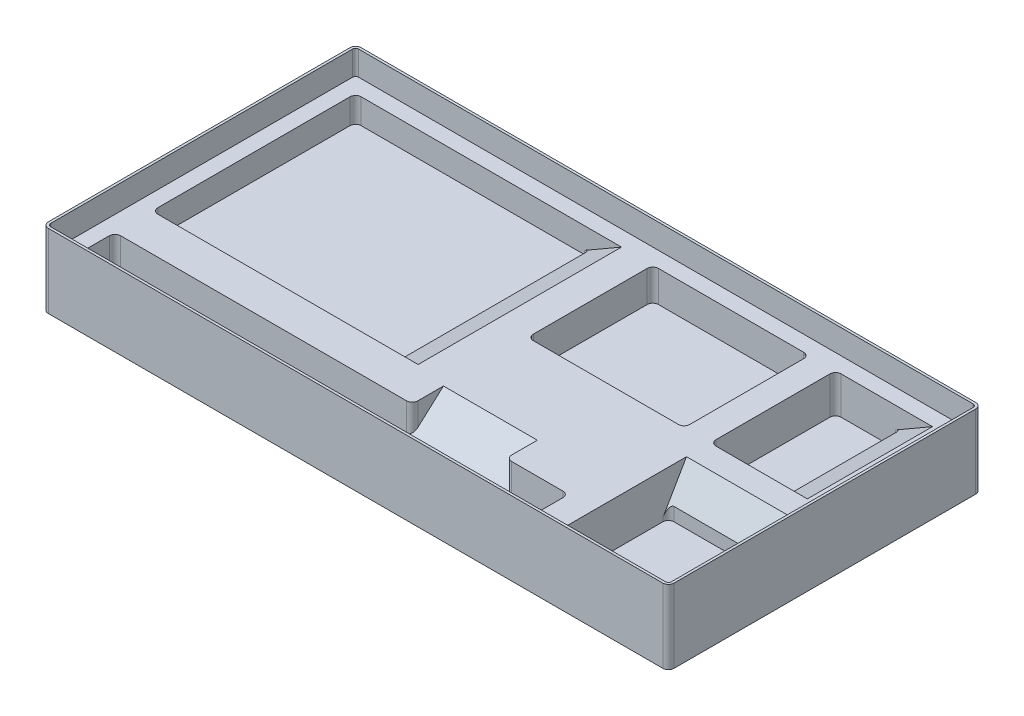
SolidWorks part; units mm, degrees
note: The reader was unsure of these and kept them because the rebuilt part matched: shared geometry of "Sketch3<3>", "Sketch3<4>", "Sketch3<5>", "Sketch3<6>", "Sketch3<7>".
other "Camera1"
ref_plane "Front Plane" through (0, 0, 0) normal (0, 0, 1) x (1, 0, 0)
ref_plane "Top Plane" through (0, 0, 0) normal (0, 1, 0) x (1, 0, 0)
ref_plane "Right Plane" through (0, 0, 0) normal (1, 0, 0) x (0, 0, -1)
sketch "Sketch1" plane through (0, 0, 0) normal (0, 1, 0) x (1, 0, 0)
  line L1 (100, -50) -> (-100, -50)
  line L2 (100, -50) -> (100, 50)
  line L3 (100, 50) -> (-100, 50)
  line L4 (-100, -50) -> (-100, 50)
  line L5 (0, 50) -> (0, -50) construction
  line L6 (100, 0) -> (-100, 0) construction
  point P0 (0, 0)
  dimension "D1" = 200
  dimension "D2" = 100
extrude "Boss-Extrude1" add sketch "Sketch1" against normal blind 0.8
sketch "Sketch2" plane through (0, 0, 0) normal (0, 1, 0) x (1, 0, 0)
  line L0 (-99.2, 49.2) -> (-99.2, -49.2)
  line L1 (-99.2, -49.2) -> (99.2, -49.2)
  line L2 (99.2, -49.2) -> (99.2, 49.2)
  line L3 (99.2, 49.2) -> (-99.2, 49.2)
  line L4 (-100, 50) -> (-100, -50)
  line L5 (-100, -50) -> (100, -50)
  line L6 (100, -50) -> (100, 50)
  line L7 (100, 50) -> (-100, 50)
  line L8 (-100, 50) -> (-100, -50)
  line L9 (-100, -50) -> (100, -50)
  line L10 (100, -50) -> (100, 50)
  line L11 (100, 50) -> (-100, 50)
  dimension "D1" = 0
  dimension "D2" = 0.8
extrude "Boss-Extrude2" add sketch "Sketch2" along normal blind 15 contours L2 L3 L0 L1 | L10 L11 L8 L9 L3 L2 L1 L0
sketch "Sketch3" plane through (0, 15, 0) normal (0, 1, 0) x (1, 0, 0)
  line L0 (0, 44.2) -> (0, 49.2) construction
  line L1 (59.2, 4.2) -> (80.2, 4.2)
  line L2 (59.2, 4.2) -> (59.2, 44.2)
  line L3 (59.2, 44.2) -> (80.2, 44.2)
  line L4 (-100, 50) -> (-100, -50)
  line L5 (-100, -50) -> (100, -50)
  line L6 (100, -50) -> (100, 50)
  line L7 (100, 50) -> (-100, 50)
  line L8 (-100, 50) -> (-100, -50) construction
  line L9 (-100, -50) -> (100, -50) construction
  line L10 (100, -50) -> (100, 50) construction
  line L11 (100, 50) -> (-100, 50) construction
  line L12 (-99.2, 49.2) -> (-99.2, -49.2)
  line L13 (-99.2, -49.2) -> (99.2, -49.2)
  line L14 (99.2, -49.2) -> (99.2, 49.2)
  line L15 (99.2, 49.2) -> (-99.2, 49.2)
  line L16 (-99.2, 49.2) -> (-99.2, -49.2) construction
  line L17 (-99.2, -49.2) -> (99.2, -49.2) construction
  line L18 (99.2, -49.2) -> (99.2, 49.2) construction
  line L19 (99.2, 49.2) -> (-99.2, 49.2) construction
  line L20 (80.2, 4.2) -> (80.2, 44.2)
  line L21 (69.7, 44.2) -> (69.7, 4.2) construction
  line L22 (59.2, 24.2) -> (80.2, 24.2) construction
  line L23 (59.2, -9.2) -> (94.2, -9.2)
  line L24 (59.2, -9.2) -> (59.2, -44.2)
  line L25 (59.2, -44.2) -> (94.2, -44.2)
  line L26 (94.2, -9.2) -> (94.2, -44.2)
  line L27 (76.7, -44.2) -> (76.7, -9.2) construction
  line L28 (59.2, -26.7) -> (94.2, -26.7) construction
  line L29 (0.8, 4.2) -> (50.8, 4.2)
  line L30 (0.8, 4.2) -> (0.8, 44.2)
  line L31 (0.8, 44.2) -> (50.8, 44.2)
  line L32 (50.8, 4.2) -> (50.8, 44.2)
  line L33 (25.8, 44.2) -> (25.8, 4.2) construction
  line L34 (0.8, 24.2) -> (50.8, 24.2) construction
  line L35 (-94.2, -20.8) -> (-19.2, -20.8)
  line L36 (-94.2, -20.8) -> (-94.2, 44.2)
  line L37 (-94.2, 44.2) -> (-19.2, 44.2)
  line L38 (-19.2, -20.8) -> (-19.2, 44.2)
  line L39 (-56.7, 44.2) -> (-56.7, -20.8) construction
  line L40 (-94.2, 11.7) -> (-19.2, 11.7) construction
  line L41 (-94.2, -44.2) -> (50.8, -44.2)
  line L42 (-94.2, -44.2) -> (-94.2, -32.7)
  line L43 (-94.2, -32.7) -> (50.8, -32.7)
  line L44 (50.8, -44.2) -> (50.8, -32.7)
  line L45 (-21.7, -32.7) -> (-21.7, -44.2) construction
  line L46 (-94.2, -38.45) -> (50.8, -38.45) construction
  line L47 (-94.2, -44.2) -> (94.2, -44.2) construction
  line L48 (-94.2, -44.2) -> (-94.2, 44.2) construction
  line L49 (-94.2, 44.2) -> (94.2, 44.2) construction
  line L50 (94.2, -44.2) -> (94.2, 44.2) construction
  line L51 (0, -49.2) -> (0, -44.2) construction
  line L52 (94.2, 0) -> (99.2, 0) construction
  line L53 (-99.2, 0) -> (-94.2, 0) construction
  line L55 (30.8, -32.7) -> (0.8, -32.7)
  line L56 (30.8, -32.7) -> (30.8, -22.7)
  line L57 (30.8, -22.7) -> (0.8, -22.7)
  line L58 (0.8, -32.7) -> (0.8, -22.7)
  line L59 (-9.2, -0.8) -> (-19.2, -0.8)
  line L60 (-9.2, -0.8) -> (-9.2, 24.2)
  line L61 (-9.2, 24.2) -> (-19.2, 24.2)
  line L62 (-19.2, -0.8) -> (-19.2, 24.2)
  line L63 (-14.2, 24.2) -> (-14.2, -0.8) construction
  line L64 (-9.2, 11.7) -> (-19.2, 11.7) construction
  line L65 (64.2, 0.8) -> (89.2, 0.8)
  line L66 (64.2, 0.8) -> (64.2, -9.2)
  line L67 (64.2, -9.2) -> (89.2, -9.2)
  line L68 (89.2, 0.8) -> (89.2, -9.2)
  line L69 (76.7, -9.2) -> (76.7, 0.8) construction
  line L70 (64.2, -4.2) -> (89.2, -4.2) construction
  point P6 (69.7, 24.2)
  point P12 (76.7, -26.7)
  point P19 (25.8, 24.2)
  point P26 (-56.7, 11.7)
  point P33 (-21.7, -38.45)
  point P53 (-14.2, 11.7)
  point P66 (76.7, -4.2)
  dimension "D3" = 75
  dimension "D4" = 65
  dimension "D5" = 145
  dimension "D6" = 11.5
  dimension "D7" = 35
  dimension "D8" = 35
  dimension "D9" = 40
  dimension "D10" = 50
  dimension "D11" = 21
  dimension "D12" = 40
  dimension "D13" = 5
  dimension "D14" = 5
  dimension "D15" = 10
  dimension "D16" = 30
  dimension "D17" = 20
  dimension "D18" = 25
  dimension "D19" = 10
  dimension "D20" = 10
  dimension "D21" = 25
  dimension "D1" = 0
  dimension "D2" = 0
extrude "Blender" cut sketch "Sketch3" against normal blind 12 contours L41 L44 L43 L42
extrude "Charcoals" cut sketch "Sketch3<3>" against normal blind 8 contours L35 L38 L37 L36
sketch "Sketch3<3>" plane through (0, 15, 0) normal (0, 1, 0) x (1, 0, 0) same geometry as "Sketch3"
extrude "Rubber" cut sketch "Sketch3<4>" against normal blind 10 contours L29 L32 L31 L30
sketch "Sketch3<4>" plane through (0, 15, 0) normal (0, 1, 0) x (1, 0, 0) same geometry as "Sketch3"
extrude "Eraser" cut sketch "Sketch3<5>" against normal blind 12 contours L1 L20 L3 L2
sketch "Sketch3<5>" plane through (0, 15, 0) normal (0, 1, 0) x (1, 0, 0) same geometry as "Sketch3"
extrude "Sharpener" cut sketch "Sketch3<6>" against normal blind 14.25 contours L26 L23 L24 L25
sketch "Sketch3<6>" plane through (0, 15, 0) normal (0, 1, 0) x (1, 0, 0) same geometry as "Sketch3"
chamfer "Chamfer1" distance 10 angle 30 3 edges at (76.7, 15, 9.2) (-19.2, 15, -11.7) (80.2, 15, -24.2)
extrude "Cut-Extrude6" cut sketch "Sketch3<7>" against normal offset from surface (9 mm away) 3 contours L58 L43 L56 L57 up to face at (-21.7, 3, 38.45)
sketch "Sketch3<7>" plane through (0, 15, 0) normal (0, 1, 0) x (1, 0, 0) same geometry as "Sketch3"
chamfer "Chamfer2" distance 10 angle 42 1 edges at (15.8, 6, 22.7)
sketch "Sketch4" plane through (0, 15, 0) normal (0, 1, 0) x (1, 0, 0)
  line L4 (-100, 50) -> (-100, -50)
  line L5 (-100, -50) -> (100, -50)
  line L6 (100, -50) -> (100, 50)
  line L7 (100, 50) -> (-100, 50)
  line L8 (-100, 50) -> (-100, -50)
  line L9 (-100, -50) -> (100, -50)
  line L10 (100, -50) -> (100, 50)
  line L11 (100, 50) -> (-100, 50)
  line L12 (-99.2, 49.2) -> (-99.2, -49.2)
  line L13 (-99.2, -49.2) -> (99.2, -49.2)
  line L14 (99.2, -49.2) -> (99.2, 49.2)
  line L15 (99.2, 49.2) -> (-99.2, 49.2)
  line L16 (-99.2, 49.2) -> (-99.2, -49.2)
  line L17 (-99.2, -49.2) -> (99.2, -49.2)
  line L18 (99.2, -49.2) -> (99.2, 49.2)
  line L19 (99.2, 49.2) -> (-99.2, 49.2)
  dimension "D1" = 0
  dimension "D2" = 0
extrude "Boss-Extrude3" add sketch "Sketch4" along normal blind 7.8
fillet "Fillet1" radius 1 4 edges at (-99.2, 18.9, -49.2) (-99.2, 18.9, 49.2) (99.2, 18.9, 49.2) (99.2, 18.9, -49.2)
fillet "Fillet2" radius 1.8 4 edges at (100, 11, -50) (100, 11, 50) (-100, 11, -50) (-100, 11, 50)
fillet "Fillet3" radius 1.8 22 edges at (59.2, 2.875, 9.2) (94.2, 2.875, 9.2) (94.2, 7.875, 44.2) (59.2, 7.875, 44.2) (59.2, 9, -4.2) (80.2, 6.1132, -4.2) (80.2, 6.1132, -44.2) (59.2, 9, -44.2) (-94.2, 9, 32.7) (-94.2, 9, 44.2) (50.8, 9, 44.2) (30.8, 10.5, 32.7) (0.8, 10.5, 32.7) (50.8, 9, 32.7) (50.8, 10, -4.2) (0.8, 10, -44.2) (0.8, 10, -4.2) (50.8, 10, -44.2) (-94.2, 11, 20.8) (-94.2, 11, -44.2) (-19.2, 8.1132, 20.8) (-19.2, 8.1132, -44.2)
